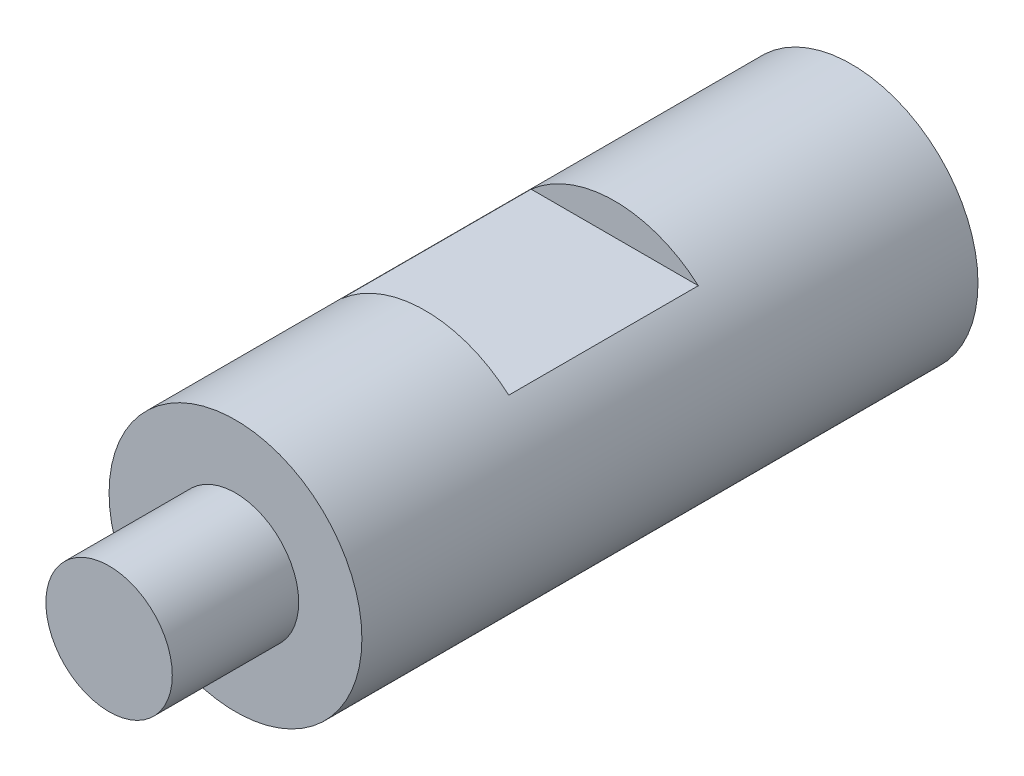
SolidWorks part; units mm, degrees
ref_plane "Front Plane" through (0, 0, 0) normal (1, 0, 0) x (0, 1, 0)
ref_plane "Top Plane" through (0, 0, 0) normal (0, 0, 1) x (0, 1, 0)
ref_plane "Right Plane" through (0, 0, 0) normal (0, 1, 0) x (-1, 0, 0)
sketch "Sketch2" plane through (0, 0, 0) normal (0, 0, 1) x (0, 1, 0)
  circle A0 centre (0, 0) radius 6.35
  dimension "D2" = 12.7
extrude "Boss-Extrude1" add sketch "Sketch2" along normal blind 30.9499
hole_wizard "Tap Drill for 1/4-20 Tap1" positions "Sketch3" profile "Sketch5" hole size "1/4-20" standard "ANSI Inch"
sketch "Sketch3" plane through (0, 0, 0) normal (0, 0, -1) x (-1, 0, 0)
  point P0 (0, 0)
sketch "Sketch5" plane through (0, 0, 0) normal (1, 0, 0) x (0, 1, 0)
  line L0 (0, 0) -> (0, 14.2338)
  line L1 (0, 14.2338) -> (2.5527, 12.7)
  line L2 (2.5527, 12.7) -> (2.5527, 0)
  line L5 (2.5527, 0) -> (0, 0)
  line L10 (0, 14.2338) -> (-2.5527, 12.7) construction
  line L11 (0, -6.35) -> (0, 107.95) construction
  dimension "Hole Dia." = 5.1054
  dimension "Hole Depth" = 12.7
  dimension "Drill Angle" = 118
sketch "Sketch6" plane through (0, 0, 30.9499) normal (0, 0, 1) x (1, 0, 0)
  circle A0 centre (0, 0) radius 3.175
  dimension "D1" = 6.35
extrude "Boss-Extrude2" add sketch "Sketch6" along normal blind 6.35
sketch "Sketch7" plane through (0, 0, 0) normal (1, 0, 0) x (0, 1, 0)
  line L0 (-6.35, 30.9499) -> (-6.35, 0) construction
  line L1 (-6.35, 21.4249) -> (6.35, 21.4249)
  line L2 (-6.35, 21.4249) -> (-6.35, 11.8999)
  line L3 (-6.35, 11.8999) -> (6.35, 11.8999)
  line L4 (6.35, 21.4249) -> (6.35, 11.8999)
  line L5 (6.35, 0) -> (6.35, 30.9499) construction
  line L6 (6.35, 30.9499) -> (-6.35, 30.9499) construction
  line L7 (0, 21.4249) -> (0, 11.8999) construction
  line L8 (-4.7625, 21.4249) -> (4.7625, 21.4249)
  line L9 (-4.7625, 21.4249) -> (-4.7625, 11.8999)
  line L10 (-4.7625, 11.8999) -> (4.7625, 11.8999)
  line L11 (4.7625, 21.4249) -> (4.7625, 11.8999)
  line L12 (-4.7625, 21.4249) -> (4.7625, 11.8999) construction
  point P16 (0, 16.6624)
  point P17 (0, 16.6624)
  dimension "D1" = 9.525
  dimension "D2" = 9.525
  dimension "D3" = 9.525
extrude "Cut-Extrude1" cut sketch "Sketch7" against normal through all and the other way through all contours L9 L1 L2 L3 | L1 L11 L3 L4 region at (0, -5.5562, 16.6624) region at (0, 5.5563, 16.6624)
